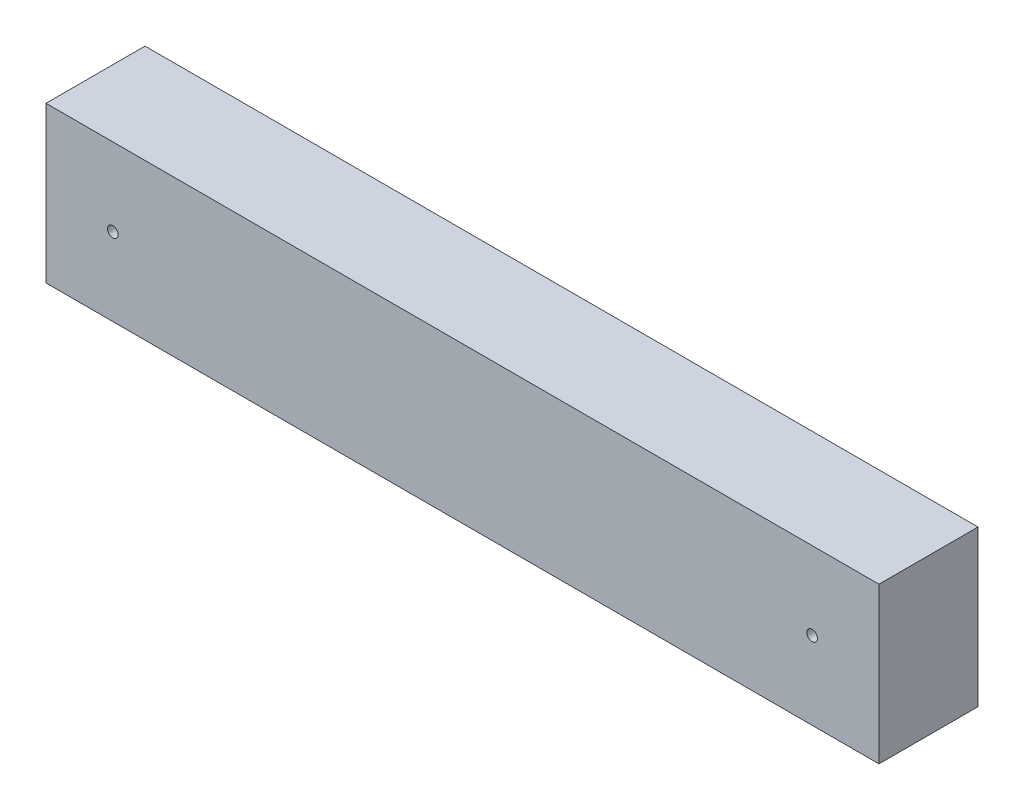
SolidWorks part; units mm, degrees
ref_plane "Front Plane" through (0, 0, 0) normal (0, 0, 1) x (1, 0, 0)
ref_plane "Top Plane" through (0, 0, 0) normal (0, 1, 0) x (1, 0, 0)
ref_plane "Right Plane" through (0, 0, 0) normal (1, 0, 0) x (0, 0, -1)
sketch "Sketch1" plane through (0, 0, 0) normal (0, 0, 1) x (1, 0, 0)
  line L1 (-373.8626, -69.85) -> (373.8626, -69.85)
  line L2 (-373.8626, -69.85) -> (-373.8626, 69.85)
  line L3 (-373.8626, 69.85) -> (373.8626, 69.85)
  line L4 (373.8626, -69.85) -> (373.8626, 69.85)
  line L5 (-373.8626, -69.85) -> (373.8626, 69.85) construction
  line L6 (-373.8626, 69.85) -> (373.8626, -69.85) construction
  point P0 (0, 0)
  dimension "D1" = 747.7252
  dimension "D2" = 139.7
extrude "Boss-Extrude1" add sketch "Sketch1" along normal blind 88.9
sketch "Sketch2" plane through (0, 0, 88.9) normal (0, 0, 1) x (1, 0, 0)
  line L1 (373.8626, 69.85) -> (-373.8626, 69.85) construction
  line L3 (-373.8626, 69.85) -> (-373.8626, -69.85) construction
  line L4 (373.8626, -69.85) -> (373.8626, 69.85) construction
  circle A0 centre (-313.8626, 0) radius 4.7625
  circle A1 centre (313.8626, 0) radius 4.7625
  dimension "D1" = 9.525
  dimension "D4" = 9.525
  dimension "D2" = 60
  dimension "D3" = 69.85
  dimension "D5" = 60
  dimension "D6" = 69.85
extrude "Cut-Extrude1" cut sketch "Sketch2" against normal through all
